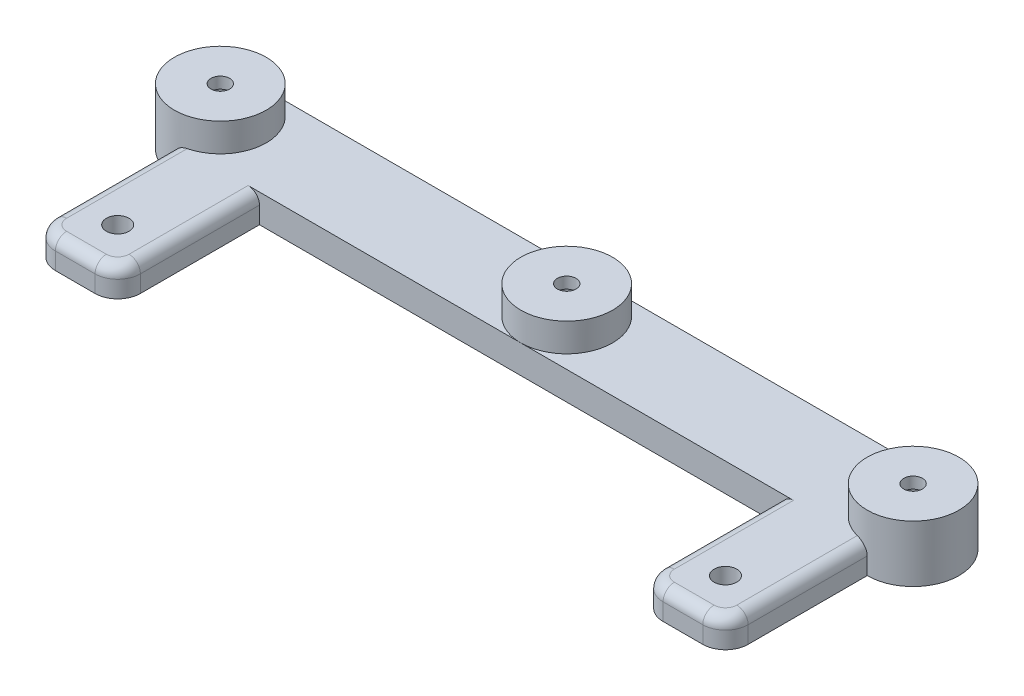
SolidWorks part; units mm, degrees
ref_plane "Front Plane" through (0, 0, 0) normal (0, 0, 1) x (1, 0, 0)
ref_plane "Top Plane" through (0, 0, 0) normal (0, 1, 0) x (1, 0, 0)
ref_plane "Right Plane" through (0, 0, 0) normal (1, 0, 0) x (0, 0, -1)
sketch "Sketch1" plane through (0, 0, 0) normal (0, 1, 0) x (1, 0, 0)
  line L1 (-61.09, 8.095) -> (61.09, 8.095)
  line L2 (-61.09, 8.095) -> (-61.09, -8.095)
  line L3 (-61.09, -8.095) -> (61.09, -8.095)
  line L4 (61.09, 8.095) -> (61.09, -8.095)
  circle A0 centre (0, 0) radius 1.645
  circle A1 centre (-61.09, 0) radius 1.645
  circle A2 centre (61.09, 0) radius 1.645
  circle A3 centre (-61.09, 0) radius 2.65
  circle A4 centre (0, 0) radius 2.65
  circle A5 centre (61.09, 0) radius 2.65
  circle A6 centre (-61.09, 0) radius 8.095
  circle A7 centre (0, 0) radius 8.095
  circle A8 centre (61.09, 0) radius 8.095
  dimension "D1" = 3.29
  dimension "D4" = 5.3
  dimension "D5" = 16.19
  dimension "D2" = 61.09
  dimension "D3" = 61.09
extrude "Boss-Extrude1" add sketch "Sketch1" along normal blind 5 contours L2 A6 A3 | L2 A6 A3 | L2 A3 A1 | L2 A3 A1 | A7 L1 A6 L3 | A7 A4 | A4 A0 | A8 L1 A7 L3 | L4 A8 A5 | L4 A8 A5 | L4 A5 A2 | L4 A5 A2 region at (-57.377, 0, 0) region at (-30.545, 0, 0) region at (-64.803, 0, 0) region at (30.545, 0, 0) region at (5.5621, 0, -5.5621) region at (-59.2581, 0, -1.8319) region at (-61.1493, 0, -2.1475) region at (64.803, 0, 0) region at (57.377, 0, 0) region at (62.9219, 0, -1.8319) region at (61.0307, 0, -2.1475) region at (-2.575, 0, 0)
extrude "Boss-Extrude2" add sketch "Sketch1<3>" along normal blind 5 from surface contours L2 A6 A3 | L2 A3 A1 | L2 A3 A1 | L2 A6 A3 | A7 A4 | A4 A0 | L4 A8 A5 | L4 A8 A5 | L4 A5 A2 | L4 A5 A2 region at (-57.377, 0, 0) region at (-64.803, 0, 0) region at (5.5621, 0, -5.5621) region at (-59.2581, 0, -1.8319) region at (-61.1493, 0, -2.1475) region at (64.803, 0, 0) region at (57.377, 0, 0) region at (62.9219, 0, -1.8319) region at (61.0307, 0, -2.1475) region at (-2.575, 0, 0) starting at face at (61.09, 5, 1.645)
sketch "Sketch1<3>" plane through (0, 0, 0) normal (0, 1, 0) x (1, 0, 0) same geometry as "Sketch1"
extrude "Cut-Extrude1" cut sketch "Sketch1<4>" along normal offset from surface (8 mm away) 2 contours L2 A3 A1 | L2 A3 A1 | A4 A0 | L4 A5 A2 | L4 A5 A2 region at (-59.2581, 0, -1.8319) region at (-61.1493, 0, -2.1475) region at (62.9219, 0, -1.8319) region at (61.0307, 0, -2.1475) region at (-2.575, 0, 0) up to face at (0, 10, 8.095)
sketch "Sketch1<4>" plane through (0, 0, 0) normal (0, 1, 0) x (1, 0, 0) same geometry as "Sketch1"
sketch "Sketch2" plane through (0, 0, 8.095) normal (0, 0, 1) x (1, 0, 0)
  line L0 (-61.09, 0) -> (61.09, 0) construction
  line L1 (-61.09, 5) -> (-46.09, 5)
  line L2 (-61.09, 5) -> (-61.09, 0)
  line L3 (-61.09, 0) -> (-46.09, 0)
  line L4 (-46.09, 5) -> (-46.09, 0)
  line L6 (61.09, 5) -> (46.09, 5)
  line L7 (61.09, 5) -> (61.09, 0)
  line L8 (61.09, 0) -> (46.09, 0)
  line L9 (46.09, 5) -> (46.09, 0)
  dimension "D1" = 15
extrude "Boss-Extrude3" add sketch "Sketch2" along normal blind 25
fillet "Fillet1" radius 4 4 edges at (-61.09, 2.5, 33.095) (-46.09, 2.5, 33.095) (61.09, 2.5, 33.095) (46.09, 2.5, 33.095)
fillet "Fillet2" radius 2 10 edges at (61.09, 5, 18.595) (59.9184, 5, 31.9234) (53.59, 5, 33.095) (47.2616, 5, 31.9234) (-46.09, 5, 18.595) (-47.2616, 5, 31.9234) (-53.59, 5, 33.095) (-59.9184, 5, 31.9234) (46.09, 5, 18.595) (-61.09, 5, 18.595)
sketch "Sketch3" plane through (0, 0, 0) normal (0, -1, 0) x (1, 0, 0)
  line L0 (-57.09, 33.095) -> (-50.09, 33.095) construction
  line L1 (46.09, 29.095) -> (46.09, 8.095) construction
  line L2 (-46.09, 29.095) -> (-46.09, 8.095) construction
  circle A0 centre (-53.59, 25.595) radius 2
  circle A1 centre (53.59, 25.595) radius 2
  point P4 (0, 0)
  dimension "D1" = 4
  dimension "D2" = 7.5
  dimension "D3" = 7.5
  dimension "D4" = 7.5
extrude "Cut-Extrude2" cut sketch "Sketch3" against normal up to next
